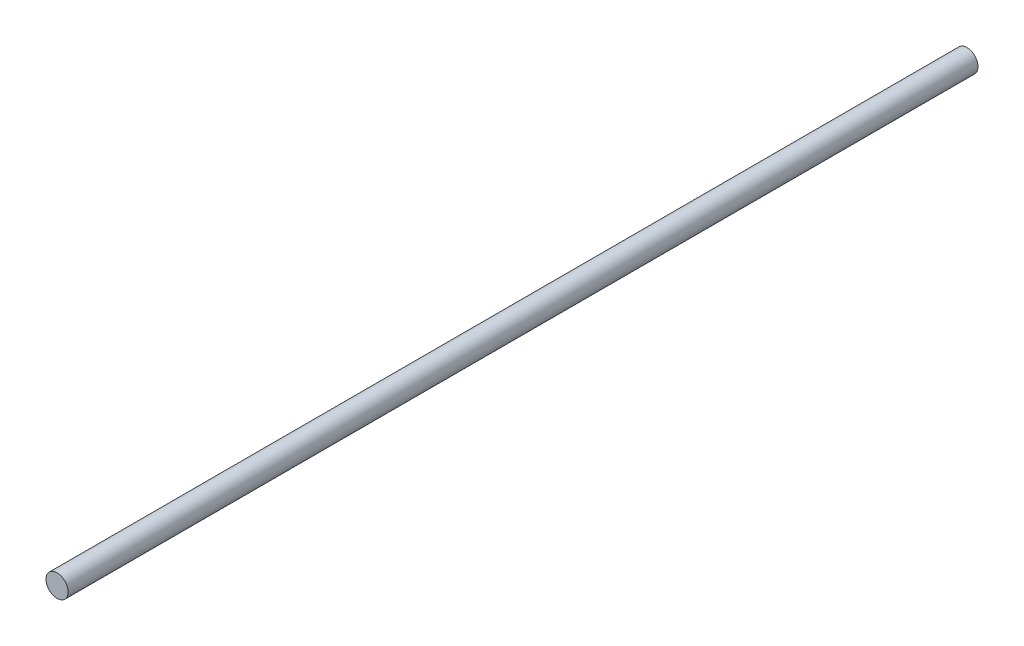
SolidWorks part; units mm, degrees
ref_plane "Front Plane" through (0, 0, 0) normal (0, 0, 1) x (1, 0, 0)
ref_plane "Top Plane" through (0, 0, 0) normal (0, 1, 0) x (1, 0, 0)
ref_plane "Right Plane" through (0, 0, 0) normal (1, 0, 0) x (0, 0, -1)
sketch "Sketch1" plane through (0, 0, 0) normal (0, 0, 1) x (1, 0, 0)
  circle A0 centre (0, 0) radius 3
extrude "Extrude1" add sketch "Sketch1" along normal blind 123 and the other way blind 123
